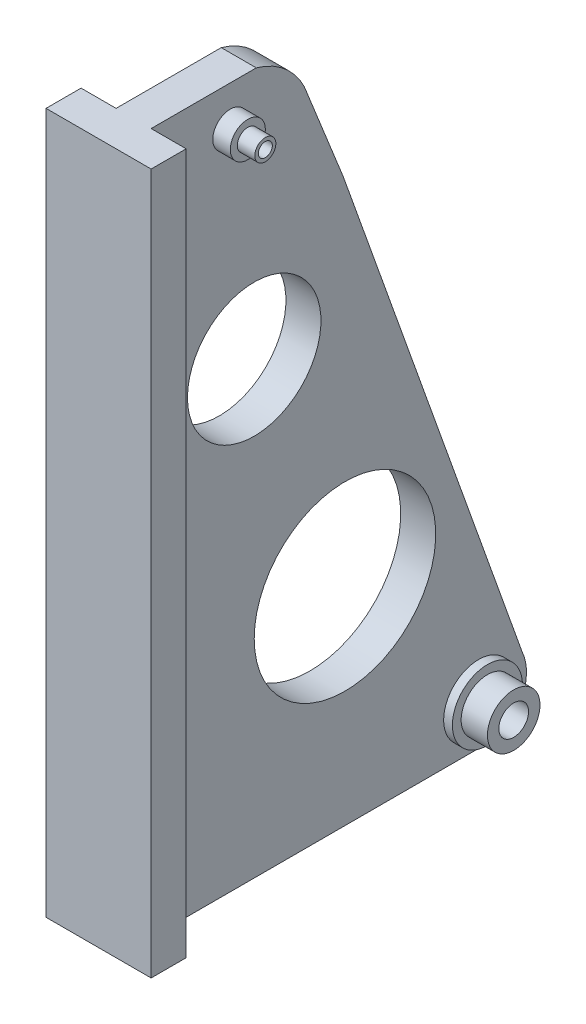
SolidWorks part; units mm, degrees
ref_plane "Plano frontal" through (0, 0, 0) normal (0, 0, 1) x (1, 0, 0)
ref_plane "Plano superior" through (0, 0, 0) normal (0, 1, 0) x (1, 0, 0)
ref_plane "Plano direito" through (0, 0, 0) normal (1, 0, 0) x (0, 0, -1)
sketch "Esboço1" plane through (0, 0, 0) normal (1, 0, 0) x (0, 0, -1)
  line L0 (0, 0) -> (0, 200)
  line L2 (0, 0) -> (110, 0)
  line L3 (115.9213, 17.653) -> (64.8176, 160.7694)
  line L4 (137.2453, 12) -> (-59.9329, 12) construction
  line L5 (103.4996, 64.5384) -> (103.4996, -33.7696) construction
  line L6 (0, 200) -> (40.0204, 200)
  line L7 (64.8176, 160.7694) -> (53.7187, 188.5)
  arc A2 (115.9213, 17.653) -> (110, 0) centre (103.4996, 12) cw
  arc A5 (40.0204, 200) -> (53.7187, 188.5) centre (34.1413, 179.0887) cw
  dimension "D1" = 200
  dimension "D2" = 110
  dimension "D5" = 12
extrude "Ressalto-extrusão1" add sketch "Esboço1" along normal blind 30
ref_plane "Plano2" through (20, 0, 0) normal (1, 0, 0) x (0, 0, -1)
sketch "Esboço7" plane through (20, 0, 0) normal (1, 0, 0) x (0, 0, -1)
  line L0 (0, 200) -> (0, 0) construction
  line L1 (10, -0.7651) -> (134.8312, -0.7651)
  line L2 (10, -0.7651) -> (10, 204.644)
  line L3 (10, 204.644) -> (134.8312, 204.644)
  line L4 (134.8312, -0.7651) -> (134.8312, 204.644)
  dimension "D1" = 10
extrude "Corte-extrusão1" cut sketch "Esboço7" along normal blind 26
ref_plane "Plano4" through (10, 0, 0) normal (-1, 0, 0) x (0, 0, 1)
sketch "Esboço9" plane through (10, 0, 0) normal (-1, 0, 0) x (0, 0, 1)
  line L0 (0, 200) -> (0, 0) construction
  line L1 (-118.1037, -3.3125) -> (-10, -3.3125)
  line L2 (-118.1037, -3.3125) -> (-118.1037, 203.1745)
  line L3 (-118.1037, 203.1745) -> (-10, 203.1745)
  line L4 (-10, -3.3125) -> (-10, 203.1745)
  dimension "D1" = 10
extrude "Corte-extrusão2" cut sketch "Esboço9" along normal blind 72
ref_plane "Plano5" through (15, 0, 0) normal (1, 0, 0) x (0, 0, -1)
sketch "Esboço10" plane through (15, 0, 0) normal (1, 0, 0) x (0, 0, -1)
  circle A0 centre (103.4996, 12) radius 10
  circle A1 centre (32.5996, 188.5) radius 5
  circle A2 centre (103.4996, 12) radius 7.5
  circle A3 centre (32.5996, 188.5) radius 3
  circle A4 centre (103.4996, 12) radius 4.25
  circle A5 centre (32.5996, 188.5) radius 2
  dimension "D3" = 10
  dimension "D4" = 6
  dimension "D5" = 4
  dimension "D6" = 20
  dimension "D7" = 15
  dimension "D8" = 8.5
  dimension "D1" = 176.5
  dimension "D2" = 70.9
extrude "Ressalto-extrusão2" add sketch "Esboço10" along normal blind 15 contours A3 A5 region at (15, 188.5, -29.6844)
extrude "Ressalto-extrusão3" add sketch "Esboço10<4>" along normal blind 10 contours A1
sketch "Esboço10<4>" plane through (15, 0, 0) normal (1, 0, 0) x (0, 0, -1) same geometry as "Esboço10"
extrude "Corte-extrusão3" cut sketch "Esboço10<5>" against normal mid plane 15 contours A5
sketch "Esboço10<5>" plane through (15, 0, 0) normal (1, 0, 0) x (0, 0, -1) same geometry as "Esboço10"
extrude "Ressalto-extrusão4" add sketch "Esboço10<6>" along normal blind 15 contours A2
sketch "Esboço10<6>" plane through (15, 0, 0) normal (1, 0, 0) x (0, 0, -1) same geometry as "Esboço10"
extrude "Ressalto-extrusão5" add sketch "Esboço10<7>" along normal mid plane 15 contours A0
sketch "Esboço10<7>" plane through (15, 0, 0) normal (1, 0, 0) x (0, 0, -1) same geometry as "Esboço10"
extrude "Corte-extrusão4" cut sketch "Esboço10<8>" against normal mid plane 20 contours A4
sketch "Esboço10<8>" plane through (15, 0, 0) normal (1, 0, 0) x (0, 0, -1) same geometry as "Esboço10"
sketch "Esboço11" plane through (15, 0, 0) normal (1, 0, 0) x (0, 0, -1)
  circle A0 centre (65.3378, 59.1415) radius 25.911
  circle A1 centre (39.4269, 128.2806) radius 19.0551
extrude "Corte-extrusão7" cut sketch "Esboço11" against normal blind 40 and the other way blind 29
extrude "Corte-extrusão8" cut sketch "Esboço10<9>" against normal mid plane 46 contours A4
sketch "Esboço10<9>" plane through (15, 0, 0) normal (1, 0, 0) x (0, 0, -1) same geometry as "Esboço10"
